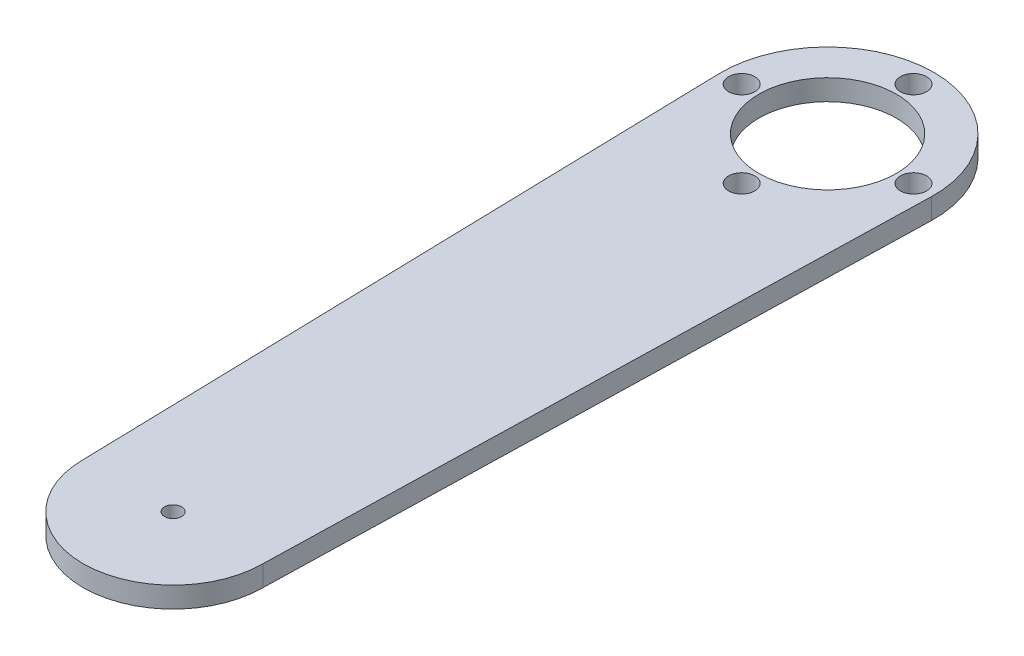
SolidWorks part; units mm, degrees
ref_plane "Front Plane" through (0, 0, 0) normal (0, 0, 1) x (1, 0, 0)
ref_plane "Top Plane" through (0, 0, 0) normal (0, 1, 0) x (1, 0, 0)
ref_plane "Right Plane" through (0, 0, 0) normal (1, 0, 0) x (0, 0, -1)
sketch "Sketch1" plane through (0, 0, 0) normal (0, 1, 0) x (1, 0, 0)
  line L0 (27.5, 0) -> (32.4898, 199.1861)
  line L1 (-27.5, 0) -> (-32.4898, 199.1861)
  arc A0 (-27.5, 0) -> (27.5, 0) centre (0, 0) ccw
  arc A3 (32.4898, 199.1861) -> (-32.4898, 199.1861) centre (0, 200) ccw
  point P8 (0, 0)
  point P9 (0, 0)
  point P10 (0, 0)
  dimension "D1" = 55
  dimension "D3" = 200
  dimension "D2" = 65
extrude "Boss-Extrude1" add sketch "Sketch1" along normal blind 6.35 contours A0 | A0 region at (0, 0, -106.0304)
sketch "Sketch2" plane through (0, 6.35, 0) normal (0, 1, 0) x (1, 0, 0)
  circle A0 centre (0, 0) radius 2.6
  dimension "D1" = 5.2
extrude "Cut-Extrude1" cut sketch "Sketch2" against normal through all
sketch "Esquisse4" plane through (0, 6.35, 0) normal (0, 1, 0) x (1, 0, 0)
  circle A0 centre (0, 200) radius 32.5
  arc A1 (32.4898, 199.1861) -> (-32.4898, 199.1861) centre (0, 200) ccw construction
sketch "Esquisse3" plane through (0, 6.35, 0) normal (0, 1, 0) x (1, 0, 0)
  circle A1 centre (0, 200) radius 21
  dimension "D1" = 42
extrude "Enlèv. mat.-Extru.2" cut sketch "Esquisse3" against normal through all
sketch "Esquisse5" plane through (0, 6.35, 0) normal (0, 1, 0) x (1, 0, 0)
  circle A0 centre (0, 200) radius 26.25
  dimension "D1" = 52.5
sketch "Esquisse7" plane through (0, 6.35, 0) normal (0, 1, 0) x (1, 0, 0)
  circle A0 centre (0, 226.25) radius 4
  circle A1 centre (0, 200) radius 26.25 construction
  circle A2 centre (26.25, 200) radius 4
  circle A3 centre (0, 173.75) radius 4
  circle A4 centre (-26.25, 200) radius 4
  point P10 (-5.2588, 174.2822)
  point P12 (0, 0)
  point P13 (0, 0)
  dimension "D1" = 8
extrude "Enlèv. mat.-Extru.3" cut sketch "Esquisse7" against normal through all
